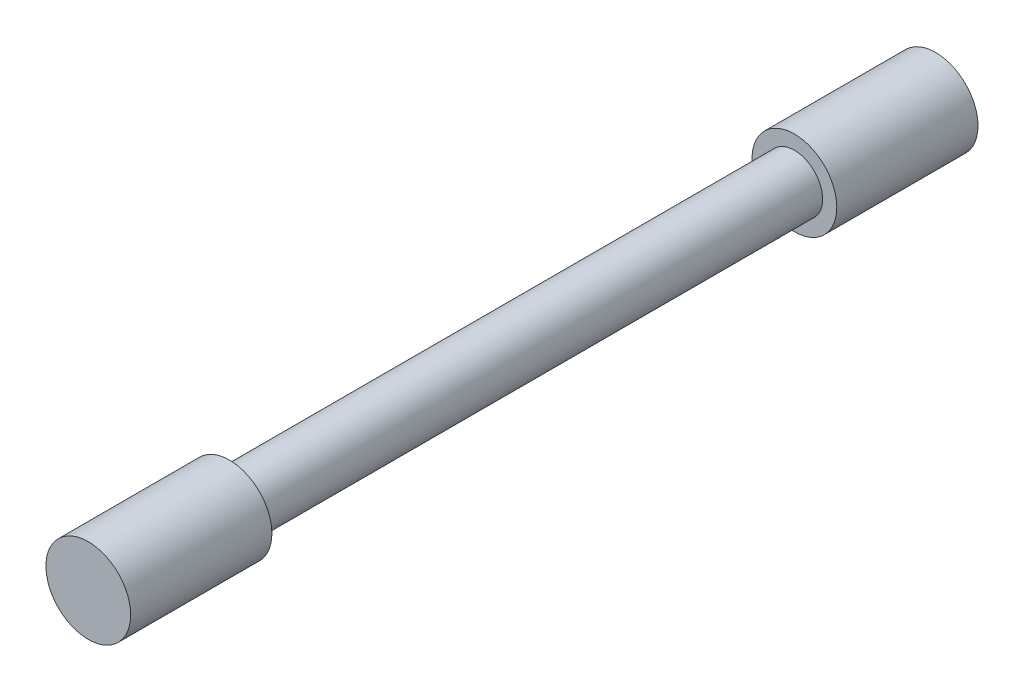
SolidWorks part; units mm, degrees
ref_plane "Front Plane" through (0, 0, 0) normal (0, 0, 1) x (1, 0, 0)
ref_plane "Top Plane" through (0, 0, 0) normal (0, 1, 0) x (1, 0, 0)
ref_plane "Right Plane" through (0, 0, 0) normal (1, 0, 0) x (0, 0, -1)
sketch "Sketch1" plane through (0, 0, 0) normal (0, 0, 1) x (1, 0, 0)
  circle A0 centre (0, 0) radius 2
  dimension "D1" = 4
extrude "Boss-Extrude1" add sketch "Sketch1" along normal blind 20 and the other way blind 20
sketch "Sketch2" plane through (0, 0, 20) normal (0, 0, 1) x (1, 0, 0)
  circle A0 centre (0, 0) radius 3
  dimension "D1" = 6
extrude "Boss-Extrude2" add sketch "Sketch2" along normal blind 10
mirror "Mirror1" about plane through (0, 0, 0) normal (0, 0, 1) of "Boss-Extrude2"
